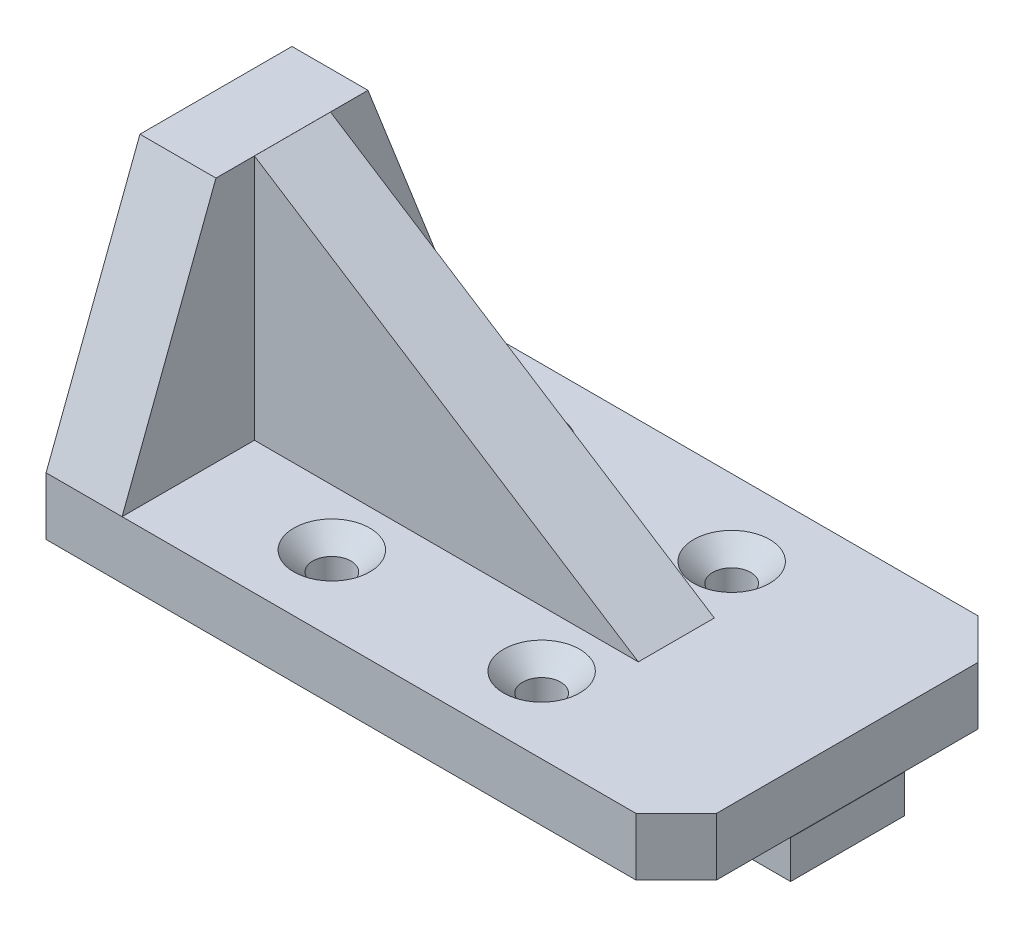
SolidWorks part; units mm, degrees
ref_plane "Front Plane" through (0, 0, 0) normal (0, 0, 1) x (1, 0, 0)
ref_plane "Top Plane" through (0, 0, 0) normal (0, 1, 0) x (1, 0, 0)
ref_plane "Right Plane" through (0, 0, 0) normal (1, 0, 0) x (0, 0, -1)
sketch "Sketch1" plane through (0, 0, 0) normal (0, 1, 0) x (1, 0, 0)
  line L0 (-1.7905, 1.2557) -> (96.7615, 1.2557)
  line L1 (96.7615, 1.2557) -> (103.4967, -5.4795)
  line L2 (103.4967, -5.4795) -> (103.4967, -49.1591)
  line L3 (103.4967, -49.1591) -> (96.7615, -55.8943)
  line L4 (96.7615, -55.8943) -> (-1.7905, -55.8943)
  line L5 (-1.7905, -55.8943) -> (-1.7905, 1.2557)
  line L6 (96.7615, 1.2557) -> (142.9173, 1.2557) construction
  line L7 (96.7615, -55.8943) -> (146.5022, -55.8943) construction
  line L8 (-1.7905, -27.3193) -> (146.5022, -27.3193) construction
  circle A0 centre (33.2615, -11.4443) radius 6.35
  circle A1 centre (68.3135, -11.4443) radius 6.35
  circle A2 centre (33.2615, -43.1943) radius 6.35
  circle A3 centre (68.3135, -43.1943) radius 6.35
  circle A4 centre (33.2615, -11.4443) radius 3.175
  circle A5 centre (68.3135, -11.4443) radius 3.175
  circle A6 centre (68.3135, -43.1943) radius 3.175
  circle A7 centre (33.2615, -43.1943) radius 3.175
  dimension "D12" = 6.35
  dimension "D13" = 12.7
  dimension "D1" = 57.15
  dimension "D2" = 98.552
  dimension "D3" = 45
  dimension "D4" = 45
  dimension "D5" = 9.525
  dimension "D6" = 12.7
  dimension "D7" = 12.7
  dimension "D8" = 35.052
  dimension "D9" = 35.052
  dimension "D10" = 35.052
  dimension "D11" = 35.052
extrude "Boss-Extrude4" add sketch "Sketch1" against normal blind 9.652 contours L5 L4 L3 L2 L1 L0 A3 A2 A1 A0 | A3 A6 | A2 A7 | A0 A4 | A1 A5 region at (50.4409, 0, 27.3193) region at (27.0911, 0, 11.4443) region at (62.1431, 0, 11.4443) region at (27.0911, 0, 43.1943) region at (62.1431, 0, 43.1943)
extrude "Cut-Extrude4" cut sketch "Sketch1<9>" against normal blind 13.462 draft 45 contours A3 A6 | A6 | A2 A7 | A7 | A4 | A0 A4 | A1 A5 | A5 region at (27.0911, 0, 11.4443) region at (62.1431, 0, 11.4443) region at (27.0911, 0, 43.1943) region at (62.1431, 0, 43.1943) region at (33.2615, 0, 11.4443) region at (68.3135, 0, 11.4443) region at (68.3135, 0, 43.1943) region at (33.2615, 0, 43.1943)
sketch "Sketch1<9>" plane through (0, 0, 0) normal (0, 1, 0) x (1, 0, 0) same geometry as "Sketch1"
sketch "Sketch2" plane through (0, 0, 0) normal (1, 0, 0) x (0, 0, -1)
  line L0 (-27.3193, 0) -> (-27.3193, 15.0741) construction
  line L1 (-5.4795, 0) -> (-49.1591, 0) construction
  line L2 (-27.3193, 0) -> (-27.3193, -28.1078) construction
  line L3 (-5.4795, -9.652) -> (-49.1591, -9.652) construction
  line L4 (-36.8443, -9.652) -> (-17.7943, -9.652)
  line L5 (-36.8443, -9.652) -> (-36.8443, -16.002)
  line L6 (-36.8443, -16.002) -> (-17.7943, -16.002)
  line L7 (-17.7943, -9.652) -> (-17.7943, -16.002)
  point P13 (-55.8943, -9.652)
  dimension "D1" = 19.05
  dimension "D2" = 19.05
  dimension "D3" = 6.35
extrude "Boss-Extrude5" add sketch "Sketch2" along normal blind 105.3337 from offset 1.778 offset against normal yes
sketch "Sketch4" plane through (0, 0, 0) normal (0, 0, 1) x (1, 0, 0)
  line L0 (10.9095, 0) -> (10.9095, 41.148)
  line L1 (96.7615, 0) -> (-1.7905, 0) construction
  line L2 (10.9095, 41.148) -> (75.0487, 0)
  line L3 (75.0487, 0) -> (10.9095, 0)
  line L4 (103.4967, -9.652) -> (103.4967, 0) construction
  dimension "D1" = 57.15
  dimension "D2" = 28.448
  dimension "D3" = 12.7
extrude "Boss-Extrude6" add sketch "Sketch4" along normal blind 12.7 from offset 21.082
sketch "Sketch5" plane through (0, 0, 0) normal (1, 0, 0) x (0, 0, -1)
  line L0 (-33.782, 41.148) -> (-46.6466, 41.148) construction
  line L1 (-21.082, 41.148) -> (-8.5466, 41.148) construction
  line L2 (-14.8143, 41.148) -> (-40.2143, 41.148)
  line L3 (-40.2143, 41.148) -> (-55.8943, 0)
  line L4 (-55.8943, 0) -> (1.2557, 0)
  line L5 (1.2557, 0) -> (-14.8143, 41.148)
  line L6 (-27.5143, 41.148) -> (-27.5143, -24.9288) construction
  line L7 (-27.5143, 41.148) -> (-27.5143, 46.4391) construction
  dimension "D1" = 25.4
extrude "Boss-Extrude7" add sketch "Sketch5" along normal blind 12.7 from offset 1.778 offset against normal yes
